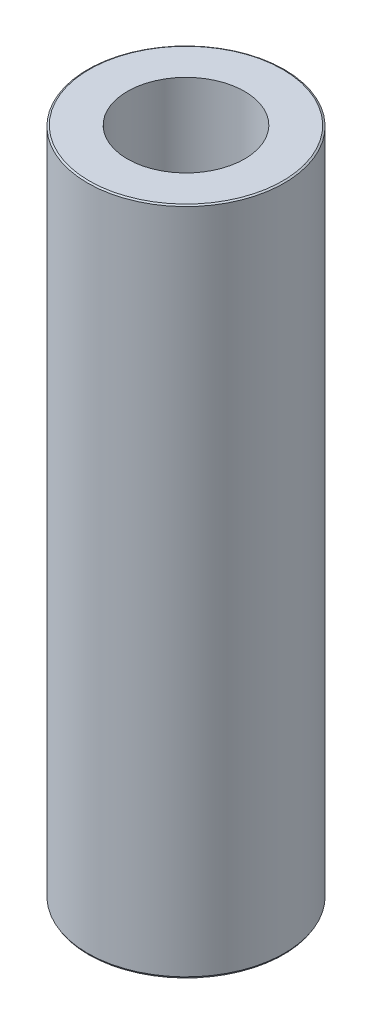
SolidWorks part; units mm, degrees
ref_plane "Front Plane" through (0, 0, 0) normal (0, 0, 1) x (1, 0, 0)
ref_plane "Top Plane" through (0, 0, 0) normal (0, 1, 0) x (1, 0, 0)
ref_plane "Right Plane" through (0, 0, 0) normal (1, 0, 0) x (0, 0, -1)
sketch "Sketch1" plane through (0, 0, 0) normal (0, 1, 0) x (1, 0, 0)
  circle A0 centre (0, 0) radius 42.5
  dimension "SHAFT_OD" = 85
extrude "Boss-Extrude1" add sketch "Sketch1" along normal blind 289.3786
sketch "Sketch2" plane through (0, 0, 0) normal (0, 1, 0) x (1, 0, 0)
  circle A0 centre (0, 0) radius 25.3236
  dimension "BORE_D" = 50.6473
extrude "Cut-Extrude1" cut sketch "Sketch2" along normal through all
chamfer "Chamfer1" distance 0.4202 angle 60 2 edges at (0, 289.3786, 42.5) (0, 0, 42.5) first distance on face at (0, 289.3786, 42.5) first distance on face at (0, 0, 25.3236)
